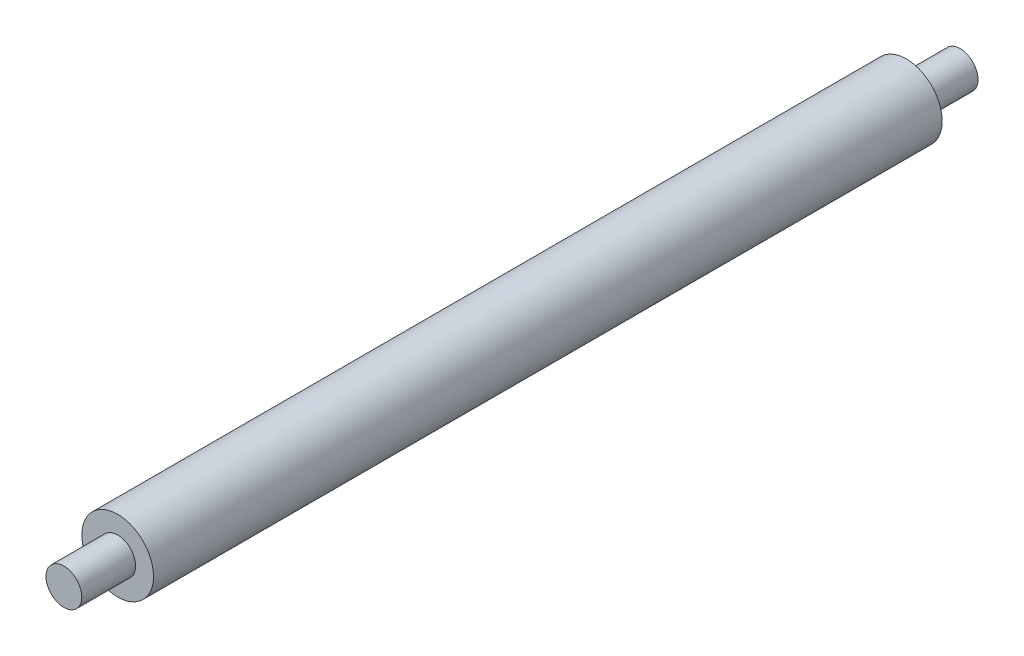
SolidWorks part; units mm, degrees
ref_plane "Front Plane" through (0, 0, 0) normal (0, 0, 1) x (1, 0, 0)
ref_plane "Top Plane" through (0, 0, 0) normal (0, 1, 0) x (1, 0, 0)
ref_plane "Right Plane" through (0, 0, 0) normal (1, 0, 0) x (0, 0, -1)
sketch "Sketch2" plane through (0, 0, 0) normal (0, 0, 1) x (1, 0, 0)
  circle A0 centre (0, 0) radius 20
  dimension "D1" = 40
extrude "Boss-Extrude1" add sketch "Sketch2" along normal blind 220 and the other way blind 220
sketch "Sketch3" plane through (0, 0, 220) normal (0, 0, 1) x (1, 0, 0)
  circle A0 centre (0, 0) radius 10
  dimension "D1" = 20
extrude "Boss-Extrude2" add sketch "Sketch3" along normal blind 30
sketch "Sketch4" plane through (0, 0, -220) normal (0, 0, -1) x (-1, 0, 0)
  circle A0 centre (0, 0) radius 10
  dimension "D1" = 20
extrude "Boss-Extrude3" add sketch "Sketch4" along normal blind 30
